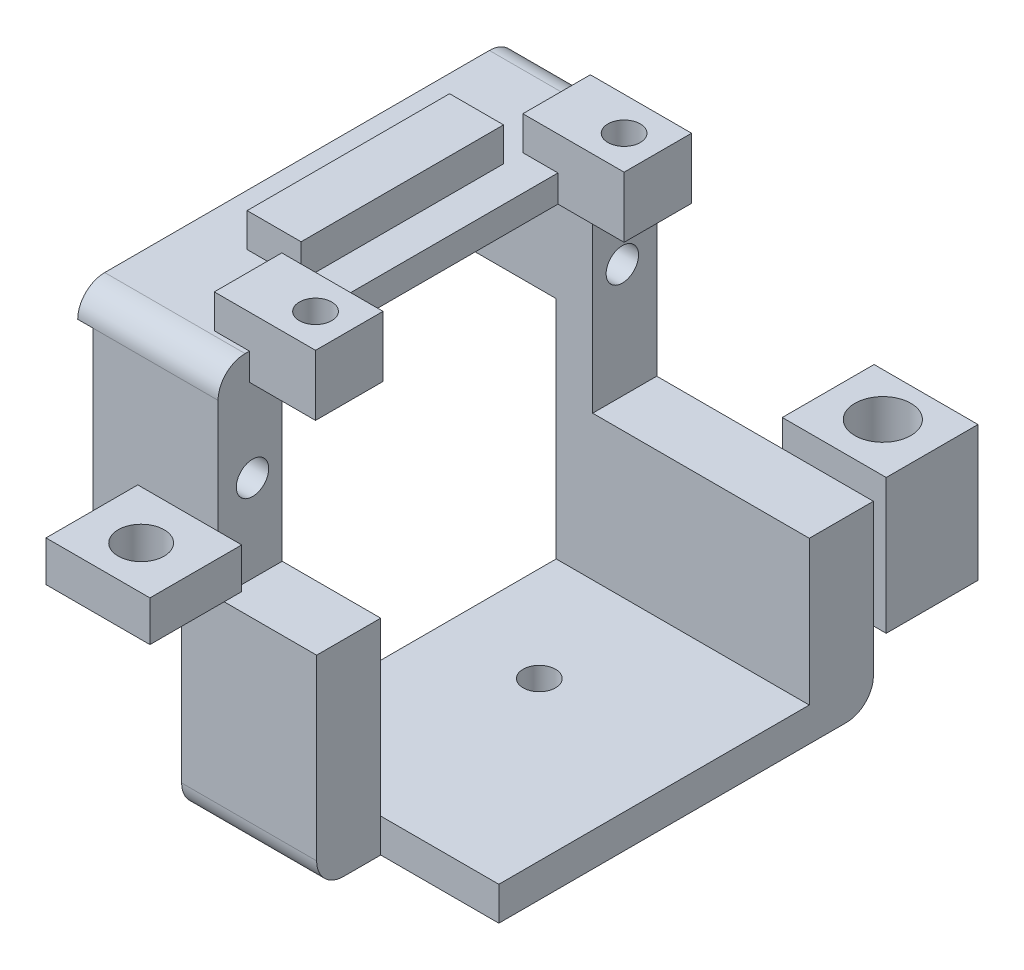
SolidWorks part; units mm, degrees
ref_plane "Front Plane" through (0, 0, 0) normal (0, 0, 1) x (1, 0, 0)
ref_plane "Top Plane" through (0, 0, 0) normal (0, 1, 0) x (1, 0, 0)
ref_plane "Right Plane" through (0, 0, 0) normal (1, 0, 0) x (0, 0, -1)
sketch "Sketch1" plane through (0, 0, 0) normal (0, 1, 0) x (1, 0, 0)
  line L0 (-1.1, 16.25) -> (-1.1, 11.5)
  line L1 (-17.65, -16.25) -> (17.65, -16.25)
  line L2 (-17.65, -16.25) -> (-17.65, 16.25)
  line L3 (-17.65, 16.25) -> (17.65, 16.25)
  line L4 (17.65, -16.25) -> (17.65, 16.25)
  line L5 (-17.65, -16.25) -> (17.65, 16.25) construction
  line L6 (-17.65, 16.25) -> (17.65, -16.25) construction
  line L7 (-1.1, 11.5) -> (17.65, 11.5)
  line L8 (-1.1, -16.25) -> (-1.1, -11.5)
  line L9 (-1.1, -11.5) -> (17.65, -11.5)
  line L10 (-1.1, 11.5) -> (-1.1, -11.5) construction
  line L11 (8.9, -11.5) -> (8.9, -16.25)
  line L12 (-8.8, 16.25) -> (-8.8, 11.5)
  line L13 (-8.8, 11.5) -> (-3.8, 11.5)
  line L14 (-3.8, 11.5) -> (-3.8, 16.25)
  line L15 (-3.8, -16.25) -> (-3.8, -11.5)
  line L16 (-3.8, -11.5) -> (-8.8, -11.5)
  line L17 (-8.8, -11.5) -> (-8.8, -16.25)
  line L18 (-8.8, 11.5) -> (-8.8, -11.5)
  line L19 (18.6, 16.25) -> (18.6, 23.05)
  line L20 (18.6, 23.05) -> (10.9, 23.05)
  line L21 (10.9, 23.05) -> (10.9, 16.25)
  line L22 (-4.35, -16.25) -> (-4.35, -23.05)
  line L23 (-4.35, -23.05) -> (3.35, -23.05)
  line L24 (3.35, -23.05) -> (3.35, -16.25)
  line L25 (18.6, 16.25) -> (10.9, 16.25)
  line L28 (-1.1, 11.5) -> (-1.1, -11.5)
  circle A0 centre (14.75, 19.85) radius 2.075
  circle A2 centre (-0.5, -19.85) radius 1.7
  point P0 (0, 0)
  point P11 (-1.1, 0)
  point P31 (14.75, 23.05)
  point P45 (-0.5, -23.05)
  dimension "D11" = 4.15
  dimension "D19" = 3.4
  dimension "D1" = 32.5
  dimension "D2" = 23
  dimension "D3" = 8.75
  dimension "D4" = 10
  dimension "D5" = 16.55
  dimension "D6" = 2.7
  dimension "D7" = 5
  dimension "D8" = 14.75
  dimension "D9" = 7.7
  dimension "D10" = 6.8
  dimension "D12" = 0.5
  dimension "D13" = 19.85
  dimension "D16" = 7.7
  dimension "D17" = 6.8
  dimension "D20" = 19.85
extrude "Boss-Extrude1" add sketch "Sketch1" against normal blind 2.5 contours L7 L28 L9 L4 | L0 L7 L4 L3 | L11 L9 L8 L1 region at (8.275, 0, -13.875) region at (8.275, 0, 0) region at (3.9, 0, 13.875)
extrude "Boss-Extrude2" add sketch "Sketch1<3>" along normal blind 12.7 contours L0 L7 L4 L3 | L11 L9 L8 L1 region at (8.275, 0, -13.875) region at (3.9, 0, 13.875)
sketch "Sketch1<3>" plane through (0, 0, 0) normal (0, 1, 0) x (1, 0, 0) same geometry as "Sketch1"
sketch "Sketch3" plane through (0, 0, 0) normal (0, 1, 0) x (1, 0, 0)
  line L0 (1.6, 16.25) -> (1.6, 11.5)
  line L1 (-17.65, 16.25) -> (17.65, 16.25) construction
  line L2 (-1.1, 11.5) -> (17.65, 11.5) construction
  line L3 (1.6, 11.5) -> (-17.65, 11.5)
  line L4 (-17.65, -16.25) -> (-17.65, 16.25) construction
  line L5 (1.6, -16.25) -> (1.6, -11.5)
  line L6 (-17.65, -16.25) -> (17.65, -16.25) construction
  line L7 (-1.1, -11.5) -> (17.65, -11.5) construction
  line L8 (1.6, -11.5) -> (-17.65, -11.5)
  line L9 (1.6, 11.5) -> (1.6, -11.5)
  line L10 (-7.65, -11.5) -> (-7.65, -16.25)
  line L11 (1.6, 16.25) -> (-17.65, 16.25)
  line L12 (-17.65, 16.25) -> (-17.65, 11.5)
  line L13 (-17.65, -11.5) -> (-17.65, -16.25)
  line L14 (-17.65, -16.25) -> (1.6, -16.25)
  line L15 (-8.8, 11.5) -> (-8.8, -11.5)
  line L16 (-8.8, 11.5) -> (-8.8, 16.25)
  line L17 (-8.8, -11.5) -> (-8.8, -16.25)
  dimension "D1" = 1.6
  dimension "D2" = 10
extrude "Boss-Extrude3" add sketch "Sketch3" along normal blind 12.7 from surface contours L11 L12 L3 L0 | L10 L14 L5 L8 region at (-3.6, 0, -13.875) region at (-3.025, 0, 13.875) starting at face at (8.275, 12.7, -13.875)
extrude "Boss-Extrude4" add sketch "Sketch3<3>" along normal blind 2 from surface contours L16 L3 L0 L11 | L3 L15 L8 | L10 L14 L5 L8 | L8 L17 L14 L10 region at (-3.6, 0, -13.875) region at (-3.6, 0, 0) region at (-3.025, 0, 13.875) region at (-8.225, 0, 13.875) starting at face at (-3.025, 25.4, 13.875)
sketch "Sketch3<3>" plane through (0, 0, 0) normal (0, 1, 0) x (1, 0, 0) same geometry as "Sketch3"
sketch "Sketch2" plane through (0, 0, 0) normal (1, 0, 0) x (0, 0, -1)
  line L0 (13.7, 6.45) -> (-13.7, 6.45) construction
  line L1 (-13.7, 19.15) -> (13.7, 19.15) construction
  circle A0 centre (13.7, 6.45) radius 1.2
  circle A1 centre (-13.7, 6.45) radius 1.2
  circle A2 centre (-13.7, 19.15) radius 1.2
  circle A3 centre (13.7, 19.15) radius 1.2
  point P4 (0, 6.45)
  dimension "D1" = 2.4
  dimension "D2" = 2.4
  dimension "D6" = 2.4
  dimension "D7" = 2.4
  dimension "D3" = 27.4
  dimension "D4" = 6.45
  dimension "D5" = 6.45
extrude "Cut-Extrude1" cut sketch "Sketch2" along normal blind 8 from surface contours A1 | A0 region at (0, 6.45, -13.7) region at (0, 6.45, 13.7) starting at face at (-1.1, 5.725, 0)
extrude "Cut-Extrude2" cut sketch "Sketch2<3>" against normal blind 8 from surface contours A3 | A2 region at (0, 19.15, 13.7) region at (0, 19.15, -13.7) starting at face at (1.6, 19.55, 0)
sketch "Sketch2<3>" plane through (0, 0, 0) normal (1, 0, 0) x (0, 0, -1) same geometry as "Sketch2"
extrude "Boss-Extrude5" add sketch "Sketch1<4>" against normal blind 3 from offset 17 contours L23 L24 L1 L22 A2 region at (1.125, 0, 16.3527)
sketch "Sketch1<4>" plane through (0, 0, 0) normal (0, 1, 0) x (1, 0, 0) same geometry as "Sketch1"
extrude "Boss-Extrude6" add sketch "Sketch1<7>" against normal blind 10 from surface contours L20 L21 L3 L19 A0 region at (11.0027, 0, -19.65) starting at face at (9.625, 12.7, -13.875)
sketch "Sketch1<7>" plane through (0, 0, 0) normal (0, 1, 0) x (1, 0, 0) same geometry as "Sketch1"
fillet "Fillet1" radius 2 4 edges at (3.9, -2.5, 16.25) (-3.6, 27.4, 16.25) (8.275, -2.5, -16.25) (-3.6, 27.4, -16.25)
sketch "Sketch5" plane through (0, 0, 0) normal (0, 1, 0) x (1, 0, 0)
  line L1 (17.65, 16.25) -> (1.6, 16.25)
  line L2 (17.65, 16.25) -> (17.65, 11.5)
  line L3 (17.65, 11.5) -> (1.6, 11.5)
  line L4 (1.6, 16.25) -> (1.6, 11.5)
extrude "Cut-Extrude3" cut sketch "Sketch5" against normal blind 2 from surface starting at face at (12.1875, 12.7, -16.7625)
sketch "Sketch6" plane through (0, 0, 0) normal (0, 1, 0) x (1, 0, 0)
  line L1 (-8.8, 11.5) -> (-1.1, 11.5)
  line L2 (-8.8, 11.5) -> (-8.8, 16.25)
  line L3 (-8.8, 16.25) -> (-1.1, 16.25)
  line L4 (-1.1, 11.5) -> (-1.1, 16.25)
extrude "Cut-Extrude4" cut sketch "Sketch6" along normal blind 4 from surface starting at face at (-4.95, 12.7, -13.875)
sketch "Sketch7" plane through (0, 0, 0) normal (0, 1, 0) x (1, 0, 0)
  line L0 (4, 11.43) -> (4, -11.43) construction
  line L2 (1.5, 13.93) -> (6.5, 13.93)
  line L3 (1.5, 13.93) -> (1.5, 8.93)
  line L4 (1.5, 8.93) -> (6.5, 8.93)
  line L5 (6.5, 13.93) -> (6.5, 8.93)
  line L6 (1.5, 13.93) -> (6.5, 8.93) construction
  line L7 (1.5, 8.93) -> (6.5, 13.93) construction
  line L8 (1.5, -8.93) -> (6.5, -8.93)
  line L9 (1.5, -8.93) -> (1.5, -13.93)
  line L10 (1.5, -13.93) -> (6.5, -13.93)
  line L11 (6.5, -8.93) -> (6.5, -13.93)
  line L12 (1.5, -8.93) -> (6.5, -13.93) construction
  line L13 (1.5, -13.93) -> (6.5, -8.93) construction
  line L21 (-5, -7.5) -> (-1, -7.5)
  line L22 (-5, -7.5) -> (-5, 7.5)
  line L23 (-5, 7.5) -> (-1, 7.5)
  line L24 (-1, -7.5) -> (-1, 7.5)
  line L25 (-5, -7.5) -> (-1, 7.5) construction
  line L26 (-5, 7.5) -> (-1, -7.5) construction
  line L27 (1.5, 13.93) -> (-1, 13.93)
  line L28 (1.5, 13.93) -> (1.5, 8.93)
  line L29 (1.5, 8.93) -> (-1, 8.93)
  line L30 (-1, 13.93) -> (-1, 8.93)
  line L31 (1.5, -13.93) -> (-1, -13.93)
  line L32 (1.5, -13.93) -> (1.5, -8.93)
  line L33 (1.5, -8.93) -> (-1, -8.93)
  line L34 (-1, -13.93) -> (-1, -8.93)
  circle A0 centre (4, 11.43) radius 1.2
  circle A1 centre (4, -11.43) radius 1.2
  point P4 (4, 0)
  point P14 (-3, 0)
  dimension "D1" = 2.4
  dimension "D2" = 2.4
  dimension "D3" = 22.86
  dimension "D4" = 5
  dimension "D5" = 5
  dimension "D6" = 5
  dimension "D7" = 5
  dimension "D8" = 4
  dimension "D9" = 3
  dimension "D10" = 15
  dimension "D11" = 4
extrude "Boss-Extrude7" add sketch "Sketch7" along normal blind 2.5 and the other way blind 2 from surface contours L21 L24 L23 L22 | L11 L8 L9 L10 A1 | L34 L31 L9 L33 | L27 L30 L29 L3 | L5 L2 L3 L4 A0 region at (4, 0, -13.8593) region at (0.25, 0, -11.43) region at (4, 0, 9.0007) region at (0.25, 0, 11.43) region at (-3, 0, 0) starting at face at (-3.6, 27.4, 0)
sketch "Sketch8" plane through (0, 0, 0) normal (0, 1, 0) x (1, 0, 0)
  line L2 (-17.65, -16.25) -> (17.65, -16.25) construction
  line L3 (8.45, 5.7) -> (3.45, 5.7)
  line L4 (8.45, 5.7) -> (8.45, 0.7)
  line L5 (8.45, 0.7) -> (3.45, 0.7)
  line L6 (3.45, 5.7) -> (3.45, 0.7)
  line L7 (8.45, 5.7) -> (3.45, 0.7) construction
  line L8 (8.45, 0.7) -> (3.45, 5.7) construction
  line L11 (-1.1, 11.5) -> (-1.1, -11.5) construction
  circle A0 centre (5.95, 3.2) radius 1.2
  dimension "D3" = 2.4
  dimension "D1" = 7.05
  dimension "D2" = 19.45
  dimension "D4" = 5
  dimension "D5" = 5
extrude "Boss-Extrude8" add sketch "Sketch8" against normal blind 4.1 from surface starting at face at (8.4833, -2.5, 3.8333)
extrude "Cut-Extrude5" cut sketch "Sketch8<2>" against normal through all both contours A0 region at (5.95, 0, -3.2)
sketch "Sketch8<2>" plane through (0, 0, 0) normal (0, 1, 0) x (1, 0, 0) same geometry as "Sketch8"
